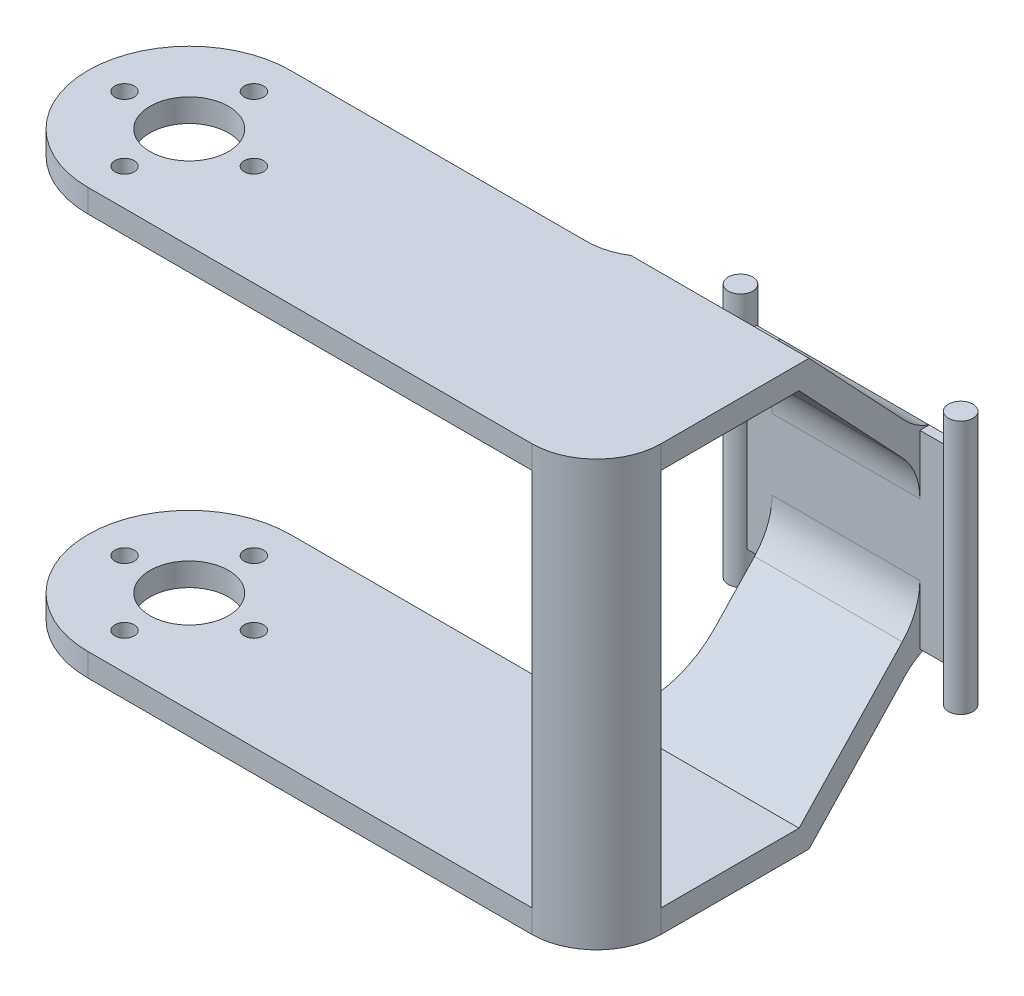
SolidWorks part; units mm, degrees
ref_plane "Front Plane" through (0, 0, 0) normal (0, 0, 1) x (1, 0, 0)
ref_plane "Top Plane" through (0, 0, 0) normal (0, 1, 0) x (1, 0, 0)
ref_plane "Right Plane" through (0, 0, 0) normal (1, 0, 0) x (0, 0, -1)
sketch "Sketch1" plane through (0, 0, 0) normal (0, 1, 0) x (1, 0, 0)
  line L1 (11.915, 0.5) -> (-11.915, 0.5)
  line L2 (11.915, 0.5) -> (11.915, -0.5)
  line L3 (11.915, -0.5) -> (-11.915, -0.5)
  line L4 (-11.915, 0.5) -> (-11.915, -0.5)
  line L5 (11.915, 0.5) -> (-11.915, -0.5) construction
  line L6 (11.915, -0.5) -> (-11.915, 0.5) construction
  point P0 (0, 0)
  dimension "D1" = 23.83
  dimension "D3" = 1
extrude "Boss-Extrude1" add sketch "Sketch1" along normal blind 20.5
ref_plane "Plane1" through (0, 10.25, 0) normal (0, 1, 0) x (1, 0, 0)
sketch "Sketch2" plane through (0, 10.25, 0) normal (0, 1, 0) x (1, 0, 0)
  line L0 (11.915, -0.5) -> (11.915, 0.5) construction
  line L1 (-11.915, 0.5) -> (-11.915, -0.5) construction
  line L2 (11.915, -0.5) -> (11.915, 0.5) construction
  line L3 (-11.915, 0.5) -> (-11.915, -0.5) construction
  circle A0 centre (-11.915, 0) radius 1.325
  circle A1 centre (11.915, 0) radius 1.325
  dimension "D1" = 2.65
extrude "Boss-Extrude2" add sketch "Sketch2" along normal mid plane 27.5
sketch "Sketch3" plane through (0, 20.5, 0) normal (0, 1, 0) x (1, 0, 0)
  line L0 (-10.688, -0.5) -> (10.688, -0.5) construction
  line L1 (-7.5, -0.5) -> (7.5, -0.5)
  line L2 (-7.5, -0.5) -> (-7.5, -26.5)
  line L3 (-7.5, -26.5) -> (7.5, -26.5)
  line L4 (7.5, -0.5) -> (7.5, -26.5)
  line L5 (0, -1000) -> (0, 49000) construction
  line L6 (-7.5, -26.5) -> (-32.5, -26.5)
  line L7 (-7.5, -26.5) -> (-7.5, -3.5)
  line L8 (-7.5, -3.5) -> (-32.5, -3.5)
  line L9 (-32.5, -26.5) -> (-32.5, -3.5)
  line L11 (-4.5, -3.5) -> (4.5, -3.5)
  line L12 (4.5, -3.5) -> (4.5, -23.5)
  line L13 (-4.5, -23.5) -> (4.5, -23.5)
  line L14 (-10.5, -23.5) -> (-29.5, -23.5)
  line L16 (-10.5, -6.5) -> (-29.5, -6.5)
  line L18 (-29.5, -23.5) -> (-29.5, -6.5) construction
  line L19 (-10.5, -23.5) -> (-10.5, -6.5) construction
  line L20 (-4.5, -3.5) -> (-4.5, -23.5) construction
  line L21 (-4.5, -3.5) -> (-4.5, -6.5)
  line L22 (-4.5, -6.5) -> (-10.5, -6.5)
  line L23 (-4.5, -23.5) -> (-10.5, -23.5)
  line L24 (-18.5, -6.5) -> (-18.5, -23.5)
  circle A0 centre (-32.5, -15) radius 11.5
  circle A1 centre (-32.5, -15) radius 4.25
  circle A2 centre (-32.5, -15) radius 7 construction
  circle A3 centre (-32.5, -8) radius 1.05
  circle A4 centre (-25.5, -15) radius 1.05
  circle A5 centre (-32.5, -22) radius 1.05
  circle A6 centre (-39.5, -15) radius 1.05
  point P10 (0, -0.5)
  line M14 (-10.688, -0.5) -> (10.688, -0.5)
  dimension "D5" = 8.5
  dimension "D6" = 14
  dimension "D7" = 2.1
  dimension "D1" = 15
  dimension "D2" = 26
  dimension "D3" = 23
  dimension "D4" = 25
  dimension "D9" = 14
  dimension "D8" = 3
extrude "Boss-Extrude3" [suppressed] add sketch "Sketch3" against normal up to surface (18.5 mm away) contours L4 L2 L3 M14 | A0 L6 L2 L8 | A5 L9 A0 A3 A1 A4 | A5 L9 A1 A3 A0 A6 | A0 L16 L22 L2 L8 | A0 L6 L2 L23 L14
sketch "Sketch4" plane through (0, 0, 0) normal (1, 0, 0) x (0, 0, -1)
  line L0 (-0.5, 20.5) -> (-12.5, 33.25)
  line L1 (-12.5, 33.25) -> (-35.5, 33.25)
  line L2 (-35.5, 33.25) -> (-35.5, 30.75)
  line L3 (-35.5, 30.75) -> (-13.5802, 30.75)
  line L4 (-13.5802, 30.75) -> (-0.5, 16.8523)
  line L5 (-0.5, 20.5) -> (-0.5, 0) construction
  line L6 (-0.5, 20.5) -> (-0.5, 0)
  line L7 (-0.5, 0) -> (-12.5, -12.75)
  line L8 (-12.5, -12.75) -> (-35.5, -12.75)
  line L9 (-35.5, -12.75) -> (-35.5, -10.25)
  line L10 (-35.5, -10.25) -> (-13.5802, -10.25)
  line L11 (-13.5802, -10.25) -> (-0.5, 3.6477)
  line L12 (-1000.5, 10.25) -> (48999.5, 10.25) construction
  line L13 (-35.5, 30.75) -> (-35.5, -10.25) construction
  point P3 (-35.5, 10.25)
  point P20 (-0.5, 10.25)
  dimension "D1" = 2.5
  dimension "D2" = 41
  dimension "D3" = 23
  dimension "D4" = 2.5
  dimension "D5" = 35
  dimension "D6" = 2.5
extrude "Boss-Extrude4" add sketch "Sketch4" along normal mid plane 16 contours L6 L0 L1 L2 L3 L4 | L11 L10 L9 L8 L7 L6
sketch "Sketch5" plane through (-8, 0, 0) normal (-1, 0, 0) x (0, 0, 1)
  line L1 (35.5, 33.25) -> (13.5802, 33.25)
  line L2 (35.5, 33.25) -> (35.5, 30.75)
  line L3 (35.5, 30.75) -> (13.5802, 30.75)
  line L4 (13.5802, 33.25) -> (13.5802, 30.75)
  line L5 (35.5, -12.75) -> (13.5802, -12.75)
  line L6 (35.5, -12.75) -> (35.5, -10.25)
  line L7 (35.5, -10.25) -> (13.5802, -10.25)
  line L8 (13.5802, -12.75) -> (13.5802, -10.25)
extrude "Boss-Extrude5" add sketch "Sketch5" along normal blind 50
sketch "Sketch6" plane through (0, 33.25, 0) normal (0, 1, 0) x (1, 0, 0)
  line L0 (-47.0401, -13.5802) -> (-47.0401, -35.5) construction
  line L1 (-58, -13.5802) -> (-8, -13.5802) construction
  line L2 (8, -35.5) -> (-58, -35.5) construction
  line L3 (-58, -24.5401) -> (8, -24.5401) construction
  line L4 (-58, -35.5) -> (-58, -13.5802) construction
  line L5 (8, -12.5) -> (8, -35.5) construction
  line L6 (-47.0401, -13.5802) -> (-58, -13.5802)
  line L7 (-58, -13.5802) -> (-58, -35.5)
  line L8 (-58, -35.5) -> (-47.0401, -35.5)
  circle A0 centre (-47.0401, -24.5401) radius 10.9599
  circle A1 centre (-47.0401, -24.5401) radius 4.25
  circle A2 centre (-47.0401, -24.5401) radius 7 construction
  circle A3 centre (-47.0401, -17.5401) radius 1.05
  circle A4 centre (-40.0401, -24.5401) radius 1.05
  circle A5 centre (-47.0401, -31.5401) radius 1.05
  circle A6 centre (-54.0401, -24.5401) radius 1.05
  point P12 (-47.0401, -24.5401)
  line M9 (-8, -13.5802) -> (-58, -13.5802)
  line M10 (-58, -13.5802) -> (-58, -35.5)
  line M11 (-58, -35.5) -> (8, -35.5)
  dimension "D1" = 8.5
  dimension "D2" = 14
  dimension "D3" = 2.1
extrude "Cut-Extrude1" cut sketch "Sketch6" against normal through all contours A1 | A6 | A3 | A4 | A5 | A0 M9 M10 | A0 L7 M11
fillet "Fillet1" radius 7 4 edges at (-8, -11.5, 13.5802) (-8, 32, 13.5802) (8, -11.5, 35.5) (8, 32, 35.5)
fillet "Fillet2" radius 7 2 edges at (0, 3.6477, 0.5) (0, 16.8523, 0.5)
fillet "Fillet3" radius 7 2 edges at (0, 20.5, 0.5) (0, 0, 0.5)
sketch "Sketch8" plane through (0, -10.25, 0) normal (0, 1, 0) x (1, 0, 0)
  line L0 (-47.0401, -13.5802) -> (-15, -13.5802) construction
  line L1 (-47.0401, -13.5802) -> (-15, -13.5802)
  line L2 (8, -28.5) -> (5, -28.5)
  line L3 (1, -35.5) -> (1, -32.5)
  arc A0 (-15, -13.5802) -> (-8, -6.5802) centre (-15, -6.5802) ccw construction
  arc A1 (1, -35.5) -> (8, -28.5) centre (1, -28.5) ccw construction
  arc A2 (-15, -13.5802) -> (-8, -6.5802) centre (-15, -6.5802) ccw
  arc A3 (1, -35.5) -> (8, -28.5) centre (1, -28.5) ccw
  circle A4 centre (-1.5277, -25.9723) radius 7
  arc M10 (1, -35.5) -> (8, -28.5) centre (1, -28.5) ccw
  dimension "D1" = 3
extrude "Boss-Extrude6" add sketch "Sketch8" along normal up to surface (41 mm away) contours A4 L3 L2 M10 up to face at (-47.0401, 30.75, 28.7901)
equation "\"D4@Sketch4\"=\"D1@Sketch4\""
equation "\"D6@Sketch4\"=\"D1@Sketch4\""
